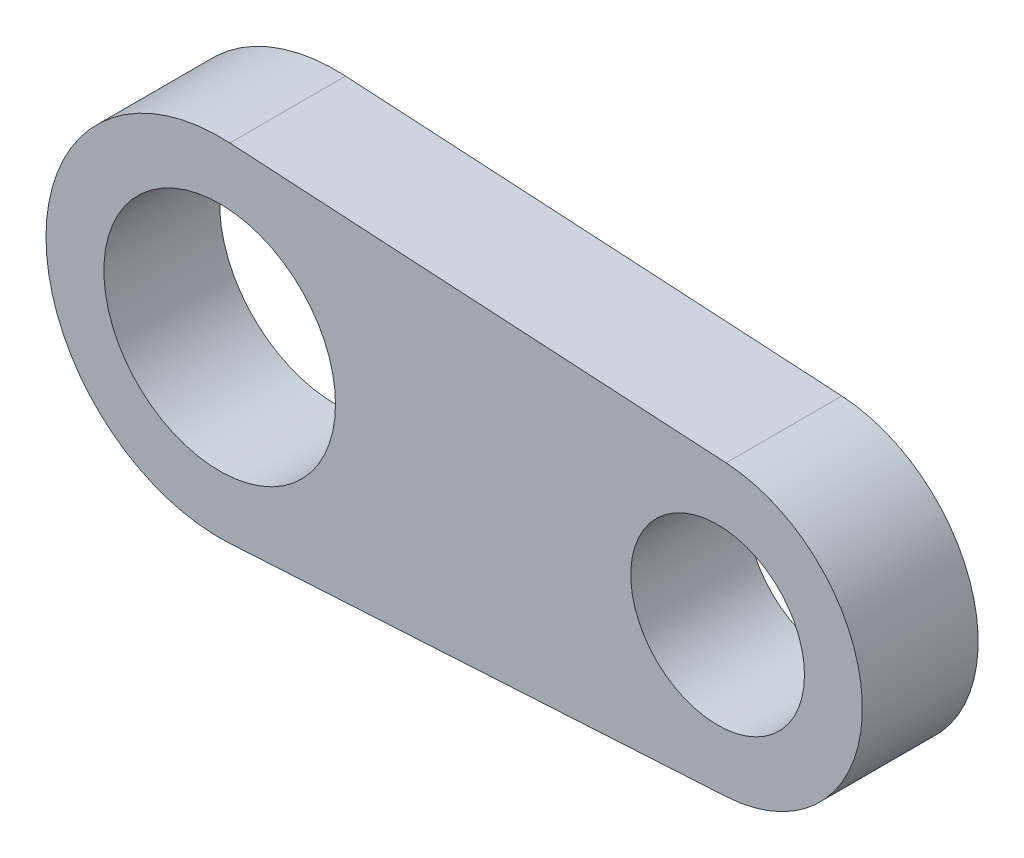
SolidWorks part; units mm, degrees
material "3003 Alloy"
ref_plane "Front Plane" through (0, 0, 0) normal (0, 0, 1) x (1, 0, 0)
ref_plane "Top Plane" through (0, 0, 0) normal (0, 1, 0) x (1, 0, 0)
ref_plane "Right Plane" through (0, 0, 0) normal (1, 0, 0) x (0, 0, -1)
sketch "Sketch1" plane through (0, 0, 0) normal (0, 0, 1) x (1, 0, 0)
  line L0 (0.8721, 14.9746) -> (43.7267, 12.4789)
  line L1 (0.8721, -14.9746) -> (43.7267, -12.4789)
  circle A0 centre (0, 0) radius 10
  circle A1 centre (43, 0) radius 7.5
  arc A2 (0.8721, 14.9746) -> (0.8721, -14.9746) centre (0, 0) ccw
  arc A3 (43.7267, -12.4789) -> (43.7267, 12.4789) centre (43, 0) ccw
  dimension "D1" = 20
  dimension "D2" = 15
  dimension "D3" = 30
  dimension "D4" = 25
  dimension "D5" = 43
extrude "Boss-Extrude1" add sketch "Sketch1" along normal blind 5 and the other way blind 5
